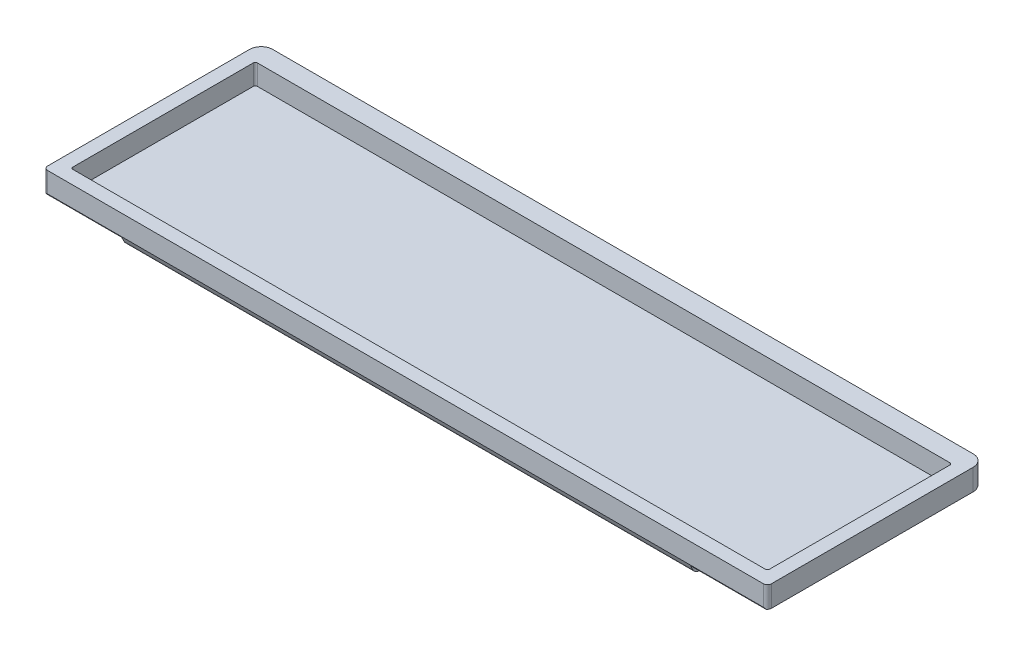
SolidWorks part; units mm, degrees
ref_plane "Front Plane" through (0, 0, 0) normal (0, 0, 1) x (1, 0, 0)
ref_plane "Top Plane" through (0, 0, 0) normal (0, 1, 0) x (1, 0, 0)
ref_plane "Right Plane" through (0, 0, 0) normal (1, 0, 0) x (0, 0, -1)
sketch "Sketch1" plane through (0, 0, 0) normal (0, 1, 0) x (1, 0, 0)
  line L1 (-178.825, 47.625) -> (178.825, 47.625)
  line L2 (-179.825, 46.625) -> (-179.825, -46.625)
  line L3 (-178.825, -47.625) -> (178.825, -47.625)
  line L4 (179.825, 46.625) -> (179.825, -46.625)
  line L5 (-179.825, 47.625) -> (179.825, -47.625) construction
  line L6 (-179.825, -47.625) -> (179.825, 47.625) construction
  arc A0 (178.825, -47.625) -> (179.825, -46.625) centre (178.825, -46.625) ccw
  arc A1 (178.825, 47.625) -> (179.825, 46.625) centre (178.825, 46.625) cw
  arc A2 (-179.825, -46.625) -> (-178.825, -47.625) centre (-178.825, -46.625) ccw
  arc A3 (-178.825, 47.625) -> (-179.825, 46.625) centre (-178.825, 46.625) ccw
  circle A4 centre (157.075, 19.175) radius 1.1
  circle A5 centre (136.925, -16.775) radius 1.1
  circle A6 centre (-153.475, 33.725) radius 1.1
  circle A7 centre (17.925, 22.275) radius 1.1
  circle A8 centre (17.875, -35.075) radius 1.1
  circle A9 centre (-130.375, -35.725) radius 1.1
  point P0 (0, 0)
  dimension "D3" = 1
  dimension "D4" = 2.2
  dimension "D7" = 2.2
  dimension "D8" = 2.2
  dimension "D9" = 2.2
  dimension "D10" = 2.2
  dimension "D11" = 2.2
  dimension "D1" = 359.65
  dimension "D2" = 95.25
  dimension "D5" = 22.75
  dimension "D6" = 28.45
  dimension "D12" = 42.9
  dimension "D13" = 30.85
  dimension "D14" = 25.35
  dimension "D15" = 161.9
  dimension "D16" = 12.55
  dimension "D17" = 161.95
  dimension "D18" = 11.9
  dimension "D19" = 49.45
  dimension "D20" = 13.9
  dimension "D21" = 26.35
sketch "Sketch2" plane through (0, 0, 0) normal (0, 1, 0) x (1, 0, 0)
  line L0 (-179.825, 46.625) -> (-179.825, -46.625) construction
  line L1 (-178.825, -47.625) -> (178.825, -47.625) construction
  line L2 (179.825, 46.625) -> (179.825, -46.625) construction
  line L3 (-178.825, 47.625) -> (178.825, 47.625) construction
  line L4 (-179.825, 46.625) -> (-179.825, -46.625)
  line L5 (-178.825, -47.625) -> (178.825, -47.625)
  line L6 (179.825, 46.625) -> (179.825, -46.625)
  line L7 (-178.825, 47.625) -> (178.825, 47.625)
  line L9 (-180.825, 57.625) -> (180.825, 57.625)
  line L10 (-186.825, 51.625) -> (-186.825, -52.625)
  line L11 (-184.825, -54.625) -> (184.825, -54.625)
  line L12 (186.825, 51.625) -> (186.825, -52.625)
  circle A0 centre (157.075, 19.175) radius 1.1 construction
  circle A1 centre (136.925, -16.775) radius 1.1 construction
  circle A2 centre (17.875, -35.075) radius 1.1 construction
  circle A3 centre (17.925, 22.275) radius 1.1 construction
  circle A4 centre (-153.475, 33.725) radius 1.1 construction
  circle A5 centre (-130.375, -35.725) radius 1.1 construction
  arc A6 (-179.825, -46.625) -> (-178.825, -47.625) centre (-178.825, -46.625) ccw construction
  arc A7 (178.825, -47.625) -> (179.825, -46.625) centre (178.825, -46.625) ccw construction
  arc A8 (179.825, 46.625) -> (178.825, 47.625) centre (178.825, 46.625) ccw construction
  arc A9 (-178.825, 47.625) -> (-179.825, 46.625) centre (-178.825, 46.625) ccw construction
  circle A10 centre (157.075, 19.175) radius 1.1
  circle A11 centre (136.925, -16.775) radius 1.1
  circle A12 centre (17.875, -35.075) radius 1.1
  circle A13 centre (17.925, 22.275) radius 1.1
  circle A14 centre (-153.475, 33.725) radius 1.1
  circle A15 centre (-130.375, -35.725) radius 1.1
  arc A16 (-179.825, -46.625) -> (-178.825, -47.625) centre (-178.825, -46.625) ccw
  arc A17 (178.825, -47.625) -> (179.825, -46.625) centre (178.825, -46.625) ccw
  arc A18 (179.825, 46.625) -> (178.825, 47.625) centre (178.825, 46.625) ccw
  arc A19 (-178.825, 47.625) -> (-179.825, 46.625) centre (-178.825, 46.625) ccw
  arc A20 (180.825, 57.625) -> (186.825, 51.625) centre (180.825, 51.625) cw
  arc A21 (-180.825, 57.625) -> (-186.825, 51.625) centre (-180.825, 51.625) ccw
  arc A22 (184.825, -54.625) -> (186.825, -52.625) centre (184.825, -52.625) ccw
  arc A23 (-186.825, -52.625) -> (-184.825, -54.625) centre (-184.825, -52.625) ccw
  point P30 (0, 0)
  dimension "D5" = 6
  dimension "D6" = 2
  dimension "D1" = 10
  dimension "D2" = 7
  dimension "D3" = 7
  dimension "D4" = 7
extrude "Boss-Extrude1" add sketch "Sketch2" along normal blind 10.5 contours L10 A23 L11 A22 L12 A20 L9 A21 A19 L7 A18 L6 A17 L5 A16 L4 region at (0, 0, -53.7235)
sketch "Sketch4" plane through (0, 0, 0) normal (0, -1, 0) x (1, 0, 0)
  line L0 (186.825, -51.625) -> (186.825, 52.625) construction
  line L1 (-180.825, -57.625) -> (180.825, -57.625) construction
  line L2 (-186.825, -51.625) -> (-186.825, 52.625) construction
  line L3 (-184.825, 54.625) -> (184.825, 54.625) construction
  line L4 (-179.825, 46.625) -> (-179.825, -46.625)
  line L5 (178.825, 47.625) -> (-178.825, 47.625)
  line L6 (179.825, -46.625) -> (179.825, 46.625)
  line L7 (-178.825, -47.625) -> (178.825, -47.625)
  line L8 (-179.825, 46.625) -> (-179.825, -46.625)
  line L10 (179.825, -46.625) -> (179.825, 46.625)
  line L11 (-178.825, -47.625) -> (178.825, -47.625)
  line L12 (186.825, -51.625) -> (186.825, 52.625)
  line L13 (-180.825, -57.625) -> (180.825, -57.625)
  line L14 (-186.825, -51.625) -> (-186.825, 52.625)
  line L15 (-184.825, 54.625) -> (184.825, 54.625)
  arc A0 (186.825, 52.625) -> (184.825, 54.625) centre (184.825, 52.625) ccw construction
  arc A1 (180.825, -57.625) -> (186.825, -51.625) centre (180.825, -51.625) ccw construction
  arc A2 (-186.825, -51.625) -> (-180.825, -57.625) centre (-180.825, -51.625) ccw construction
  arc A3 (-184.825, 54.625) -> (-186.825, 52.625) centre (-184.825, 52.625) ccw construction
  arc A4 (-179.825, -46.625) -> (-178.825, -47.625) centre (-178.825, -46.625) ccw
  arc A5 (-178.825, 47.625) -> (-179.825, 46.625) centre (-178.825, 46.625) ccw
  arc A6 (179.825, 46.625) -> (178.825, 47.625) centre (178.825, 46.625) ccw
  arc A7 (178.825, -47.625) -> (179.825, -46.625) centre (178.825, -46.625) ccw
  arc A8 (-179.825, -46.625) -> (-178.825, -47.625) centre (-178.825, -46.625) ccw
  arc A9 (-178.825, 47.625) -> (-179.825, 46.625) centre (-178.825, 46.625) ccw
  arc A10 (179.825, 46.625) -> (178.825, 47.625) centre (178.825, 46.625) ccw
  arc A11 (178.825, -47.625) -> (179.825, -46.625) centre (178.825, -46.625) ccw
  arc A12 (186.825, 52.625) -> (184.825, 54.625) centre (184.825, 52.625) ccw
  arc A13 (180.825, -57.625) -> (186.825, -51.625) centre (180.825, -51.625) ccw
  arc A14 (-186.825, -51.625) -> (-180.825, -57.625) centre (-180.825, -51.625) ccw
  arc A15 (-184.825, 54.625) -> (-186.825, 52.625) centre (-184.825, 52.625) ccw
  arc M9 (-178.825, -47.625) -> (-179.825, -46.625) centre (-178.825, -46.625) cw
  line M10 (-179.825, -46.625) -> (-179.825, 46.625)
  arc M11 (-179.825, 46.625) -> (-178.825, 47.625) centre (-178.825, 46.625) cw
  line M12 (-178.825, 47.625) -> (178.825, 47.625)
  arc M13 (178.825, 47.625) -> (179.825, 46.625) centre (178.825, 46.625) cw
  line M14 (179.825, 46.625) -> (179.825, -46.625)
  arc M15 (179.825, -46.625) -> (178.825, -47.625) centre (178.825, -46.625) cw
  line M16 (178.825, -47.625) -> (-178.825, -47.625)
  line M17 (-186.825, 52.625) -> (-186.825, -51.625)
  arc M18 (-186.825, -51.625) -> (-180.825, -57.625) centre (-180.825, -51.625) ccw
  line M19 (-180.825, -57.625) -> (180.825, -57.625)
  arc M20 (180.825, -57.625) -> (186.825, -51.625) centre (180.825, -51.625) ccw
  line M21 (186.825, -51.625) -> (186.825, 52.625)
  arc M22 (186.825, 52.625) -> (184.825, 54.625) centre (184.825, 52.625) ccw
  line M23 (184.825, 54.625) -> (-184.825, 54.625)
  arc M24 (-184.825, 54.625) -> (-186.825, 52.625) centre (-184.825, 52.625) ccw
  dimension "D1" = 0
extrude "Boss-Extrude3" add sketch "Sketch4" along normal blind 10.5 contours M24 M17 M18 M19 M20 M21 M22 M23 M16 M9 M10 M11 M12 M13 M14 M15 | M9 M16 M15 M14 M13 M12 M11 M10 region at (0, 0, 0) region at (182.3089, 0, -53.1089)
sketch "Sketch5" plane through (186.825, 0, 0) normal (1, 0, 0) x (0, 0, -1)
  line L0 (-54.625, 0) -> (57.625, 0) construction
  line L1 (-54.625, 10.5) -> (-54.625, -10.5) construction
  line L2 (57.625, 10.5) -> (57.625, -10.5) construction
  line L3 (-54.625, 0) -> (-52.625, -4)
  line L4 (-52.625, 10.5) -> (-52.625, -10.5) construction
  line L5 (-52.625, -4) -> (-38.0048, -10.5)
  line L6 (51.625, -10.5) -> (-52.625, -10.5) construction
  line L7 (-38.0048, -10.5) -> (57.625, 0)
  line L8 (-54.625, 0) -> (57.625, 0)
  line L9 (-54.625, 0) -> (-54.625, -10.5)
  line L10 (-54.625, -10.5) -> (-38.0048, -10.5)
  line L11 (57.625, -10.5) -> (57.625, 0)
  line L12 (57.625, -10.5) -> (-38.0048, -10.5)
  line M5 (-52.625, 10.5) -> (-52.625, -10.5)
  line M6 (-52.625, -10.5) -> (51.625, -10.5)
  line M7 (51.625, -10.5) -> (51.625, 10.5)
  dimension "D1" = 4
  dimension "D2" = 16
extrude "Cut-Extrude1" cut sketch "Sketch5" against normal blind 400 contours L9 L10 L3 M5 | L5 M5 M6 | L7 M6 M7 | L12 L11 L7 M7 region at (186.825, -6.1716, 53.7034) region at (186.825, -8.3333, 47.7516) region at (186.825, -7.2196, -21.7484) region at (186.825, -5.4129, -54.6574)
fillet "Fillet2" radius 3 2 edges at (0, -10.5, 38.0048) (0, -4, 52.625)
ref_plane "Plane1" through (0, -10.5, 0) normal (0, 1, 0) x (1, 0, 0)
sketch "Sketch7" plane through (0, -10.5, 0) normal (0, 1, 0) x (1, 0, 0)
  line L0 (-180.825, 57.625) -> (180.825, 57.625) construction
  line L1 (146.825, 57.625) -> (192.2327, 57.625)
  line L2 (146.825, 57.625) -> (146.825, -54.625)
  line L3 (146.825, -54.625) -> (192.2327, -54.625)
  line L4 (192.2327, 57.625) -> (192.2327, -54.625)
  line L5 (-184.825, -54.625) -> (184.825, -54.625) construction
  line L6 (186.825, 51.625) -> (186.825, -52.625) construction
  line L7 (-186.825, 51.625) -> (-186.825, -52.625) construction
  line L8 (-146.825, 57.625) -> (-200.5924, 57.625)
  line L9 (-146.825, 57.625) -> (-146.825, -54.625)
  line L10 (-146.825, -54.625) -> (-200.5924, -54.625)
  line L11 (-200.5924, 57.625) -> (-200.5924, -54.625)
  dimension "D1" = 40
  dimension "D2" = 40
extrude "Cut-Extrude2" cut sketch "Sketch7" along normal blind 10
